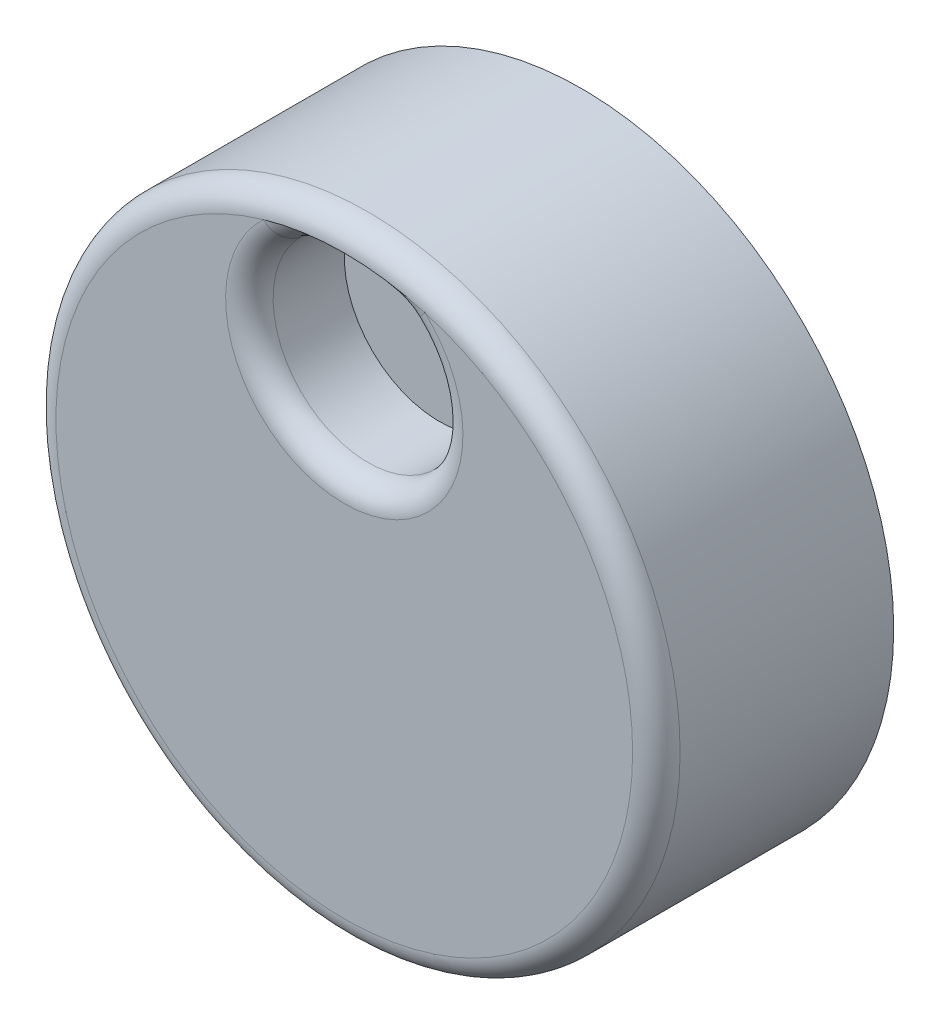
SolidWorks part; units mm, degrees
ref_plane "Plan de face" through (0, 0, 0) normal (0, 0, 1) x (1, 0, 0)
ref_plane "Plan de dessus" through (0, 0, 0) normal (0, 1, 0) x (1, 0, 0)
ref_plane "Plan de droite" through (0, 0, 0) normal (1, 0, 0) x (0, 0, -1)
sketch "Esquisse1" plane through (0, 0, 0) normal (0, 0, 1) x (1, 0, 0)
  circle A0 centre (0, 0) radius 13.15
  dimension "D1" = 26.3
extrude "Boss.-Extru.1" add sketch "Esquisse1" along normal blind 10
fillet "Congé1" radius 1 1 edges at (13.15, 0, 10)
sketch "Esquisse2" plane through (0, 0, 10) normal (0, 0, 1) x (1, 0, 0)
  line L0 (0, 0) -> (0, 8) construction
  circle A0 centre (0, 8) radius 4
  dimension "D1" = 8
  dimension "8" = 8
extrude "Enlèv. mat.-Extru.1" cut sketch "Esquisse2" against normal blind 4
fillet "Congé2" radius 1 1 edges at (4, 8, 10)
sketch "Esquisse3" plane through (0, 0, 0) normal (0, 0, -1) x (-1, 0, 0)
  circle A0 centre (0, 0) radius 3.125
  dimension "D1" = 6.25
extrude "Enlèv. mat.-Extru.2" cut sketch "Esquisse3" against normal blind 5.2
